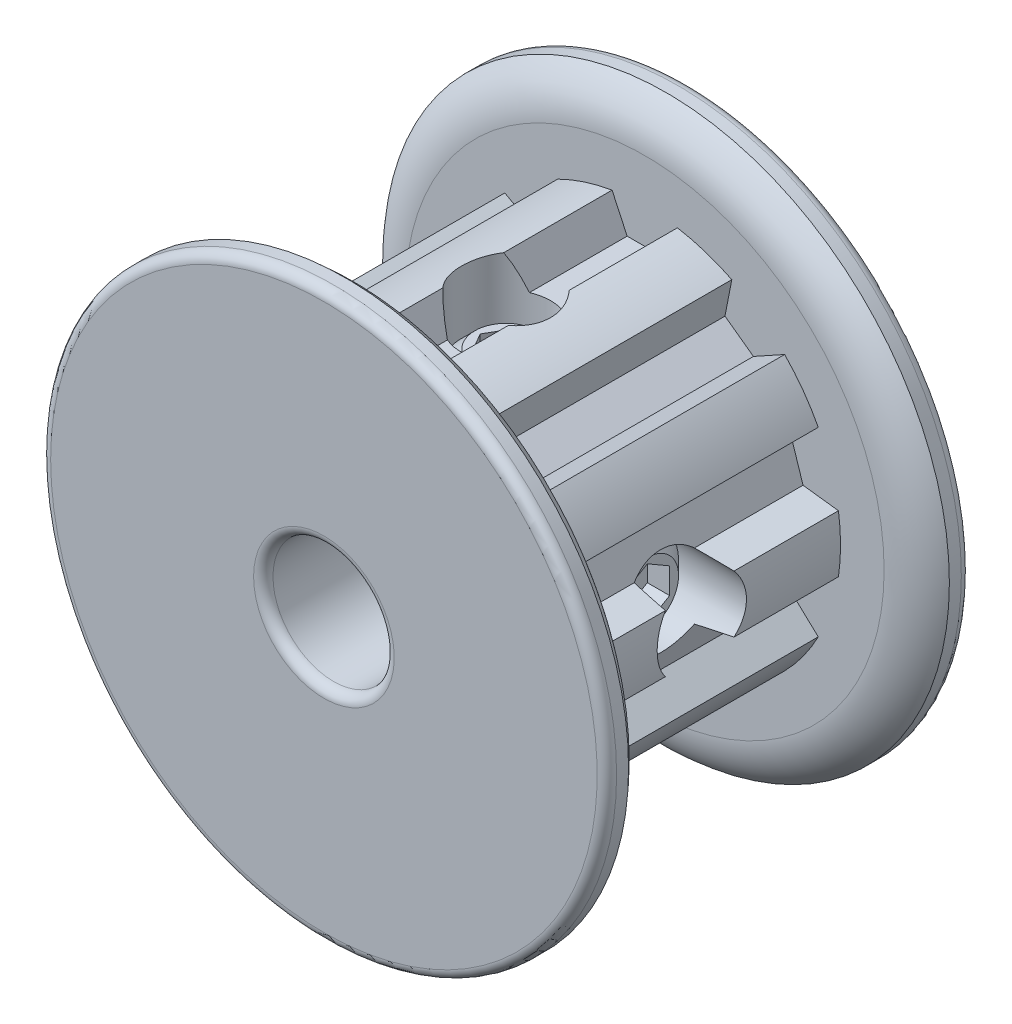
SolidWorks part; units mm, degrees
note: '?' marks a value the reader was unsure of.
ref_plane "Front Plane" through (0, 0, 0) normal (0, 0, 1) x (1, 0, 0)
ref_plane "Top Plane" through (0, 0, 0) normal (0, 1, 0) x (1, 0, 0)
ref_plane "Right Plane" through (0, 0, 0) normal (1, 0, 0) x (0, 0, -1)
sketch "Sketch1" plane through (0, 0, 0) normal (0, 0, 1) x (1, 0, 0)
  line L0 (-1.2827, 7.5819) -> (-0.6905, 6.3119)
  line L1 (-0.6905, 6.3119) -> (0.6905, 6.3119)
  line L2 (0.6905, 6.3119) -> (1.2827, 7.5819)
  line L3 (-1.2827, 7.5819) -> (1.2827, 7.5819)
  line L4 (0, 0) -> (0, 6.3119) construction
  line L5 (0, 6.3119) -> (0, 8.5979) construction
  circle A0 centre (0, 0) radius 8.0899 construction
  circle A1 centre (0, 0) radius 11.1125 construction
  circle A2 centre (0, 0) radius 7.6896 construction
  point P6 (0, 7.5819)
  point P11 (0, 8.0899)
  point P13 (0, 11.1125)
  point P14 (0, 7.6896)
  dimension "D1" = 1.016
  dimension "PD" = 16.1798
  dimension "D2" = 0.508
  dimension "OD" = 22.225
  dimension "b" = 50
  dimension "bt" = 2.5654
  dimension "ht" = 1.27
  dimension "hs" = 2.286
sketch "Sketch2" plane through (0, 0, 0) normal (1, 0, 0) x (0, 0, -1)
  line L0 (-7.1501, 2.3812) -> (7.1501, 2.3812)
  line L3 (-7.1501, 2.3812) -> (-7.1501, 11.1125)
  line L4 (-7.1501, 11.1125) -> (-5.4483, 11.1125) construction
  line L5 (-5.4483, 11.1125) -> (-5.4483, 7.6896) construction
  line L6 (-5.4483, 7.6896) -> (5.4483, 7.6896)
  line L7 (5.4483, 7.6896) -> (5.4483, 11.1125) construction
  line L8 (5.4483, 11.1125) -> (7.1501, 11.1125) construction
  line L9 (7.1501, 11.1125) -> (7.1501, 2.3812)
  line L10 (-7.1501, 0) -> (7.1501, 0) construction
  line L13 (-7.1501, 11.1125) -> (-6.2992, 11.1125)
  line L14 (-5.4483, 9.4011) -> (-5.4483, 7.6896)
  line L15 (5.4483, 7.6896) -> (5.4483, 9.4011)
  line L16 (6.2992, 11.1125) -> (7.1501, 11.1125)
  arc A0 (-5.4483, 9.4011) -> (-6.2992, 11.1125) centre (-7.5949, 9.4011) ccw
  arc A1 (5.4483, 9.4011) -> (6.2992, 11.1125) centre (7.5949, 9.4011) cw
  point P12 (-5.4483, 9.4011)
  point P14 (-6.2992, 11.1125)
  point P20 (5.4483, 9.4011)
  point P21 (6.2992, 11.1125)
  point P25 (5.4483, 0)
  point P26 (-5.4483, 0)
  dimension "OA" = 14.3002
  dimension "Bore" = 4.7625
  dimension "Outside Width" = 14.3002
  dimension "Inside Width" = 10.8966
revolve "Revolve1" add sketch "Sketch2" angle 360 mid plane about L10
sketch "Sketch3" plane through (0, 0, 0) normal (0, 0, 1) x (1, 0, 0)
  line L0 (-0.6905, 6.3119) -> (0.6905, 6.3119) construction
  line L1 (0.6905, 6.3119) -> (1.2827, 7.5819) construction
  line L2 (-1.2827, 7.5819) -> (-0.6905, 6.3119) construction
  line L3 (-0.6905, 6.3119) -> (0.6905, 6.3119)
  line L4 (0.6905, 6.3119) -> (1.2827, 7.5819)
  line L5 (-1.2827, 7.5819) -> (-0.6905, 6.3119)
  circle A0 centre (0, 0) radius 7.6896 construction
  arc A1 (1.2827, 7.5819) -> (-1.2827, 7.5819) centre (0, 0) ccw
extrude "Cut-Extrude1" cut sketch "Sketch3" against normal up to vertex (5.4483 mm away) from vertex at 5.4483 starting at point (0, 7.6896, 5.4483)
pattern_circular "CirPattern1" count 10 over 360 about axis through (0, 0, 0) along (0, 0, 1) of "Cut-Extrude1"
fillet "Fillet1" radius 0.381 4 edges at (2.3812, 0, -7.1501) (11.1125, 0, -7.1501) (11.1125, 0, 7.1501) (2.3812, 0, 7.1501)
sketch "Sketch5" plane through (0, 0, 0) normal (0, 1, 0) x (1, 0, 0)
  line L1 (1.2827, 0) -> (-1.2827, 0) construction
  line L2 (1.2827, 5.4483) -> (1.2827, -5.4483) construction
  line L3 (-1.2827, 5.4483) -> (-1.2827, -5.4483) construction
  circle A0 centre (0, 0) radius 1.7526
extrude "Cut-Extrude2" cut sketch "Sketch5" along normal through all
sketch "Sketch6" plane through (0, 0, 0) normal (1, 0, 0) x (0, 0, -1)
  line L0 (0, 5.5499) -> (0, 3.1433)
  line L1 (6.7691, 2.3812) -> (-6.7691, 2.3812) construction
  line L3 (1.7526, 6.3119) -> (-1.7526, 6.3119) construction
  line L4 (-1.6108, 6.3119) -> (-1.7526, 6.3119) construction
  line L5 (1.7526, 6.3119) -> (1.6108, 6.3119) construction
  line L6 (0, 5.5499) -> (-1.2268, 5.5499)
  line L7 (-1.2268, 5.5499) -> (-1.7526, 5.0241)
  line L8 (-1.7526, 5.0241) -> (-1.7526, 3.669)
  line L9 (-1.7526, 3.669) -> (-1.2268, 3.1433)
  line L10 (-1.2268, 3.1433) -> (0, 3.1433)
  point P12 (0, 2.3813)
  point P19 (0, 6.3119)
  dimension "D1" = 0.762
  dimension "D2" = 0.762
  dimension "D3" = 135
  dimension "D4" = 0.5258
revolve "Revolve2" add sketch "Sketch6" angle 360 about L0
sketch "Sketch7" plane through (0, 5.5499, 0) normal (0, 1, 0) x (1, 0, 0)
  line L1 (1.0119, 0) -> (0.5059, 0.8763)
  line L2 (0.5059, 0.8763) -> (-0.5059, 0.8763)
  line L3 (-0.5059, 0.8763) -> (-1.0119, 0)
  line L4 (-1.0119, 0) -> (-0.5059, -0.8763)
  line L5 (-0.5059, -0.8763) -> (0.5059, -0.8763)
  line L6 (0.5059, -0.8763) -> (1.0119, 0)
  circle A0 centre (0, 0) radius 0.8763 construction
  dimension "D1" = 1.7526
extrude "Cut-Extrude3" cut sketch "Sketch7" against normal blind 0.8763
pattern_circular "CirPattern2" count 2 over 270 about axis through (0, 0, 0) along (0, 0, 1) of "Cut-Extrude2", "Revolve2", "Cut-Extrude3"
ref_axis "Center Axis 1" through (0, 0, -6.7691) along (0, 0, 1)?
ref_plane "Contact Plane 1" through (0, 0, 7.1501) normal (0, 0, 1) x (1, 0, 0)
ref_plane "Contact Plane 2" through (0, 0, -7.1501) normal (0, 0, -1) x (-1, 0, 0)
equation "\"D4@Sketch6\" = \"Set Screw Dia@Sketch5\" * .15"
equation "\"D1@Sketch7\" = \"Set Screw Dia@Sketch5\" / 2"
equation "\"D1@Cut-Extrude3\" = \"Set Screw Dia@Sketch5\" / 4"
